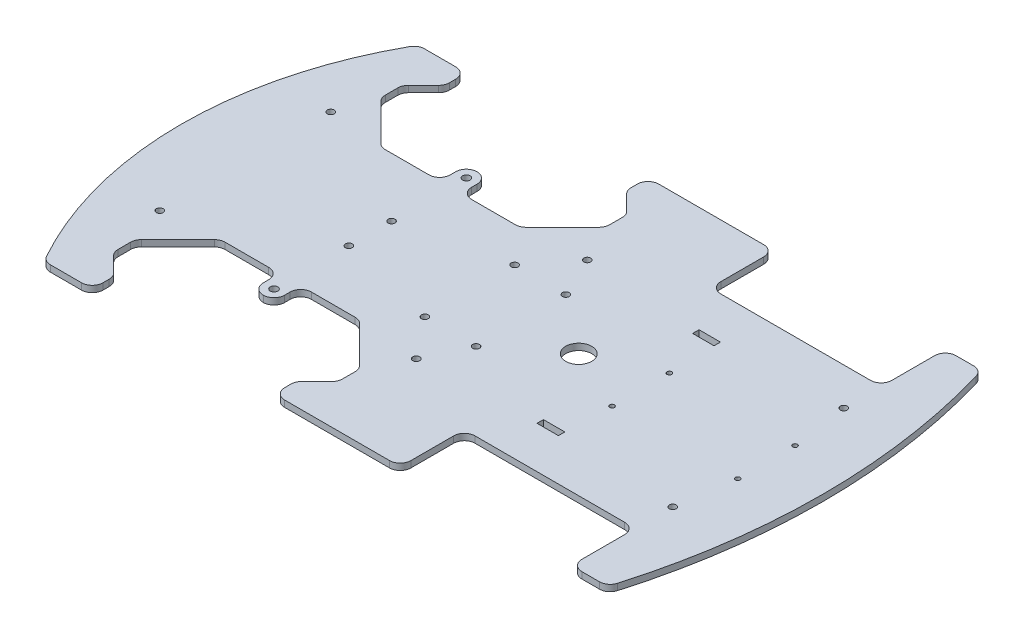
SolidWorks part; units mm, degrees
ref_plane "Front Plane" through (0, 0, 0) normal (0, 0, 1) x (1, 0, 0)
ref_plane "Top Plane" through (0, 0, 0) normal (0, 1, 0) x (1, 0, 0)
ref_plane "Right Plane" through (0, 0, 0) normal (1, 0, 0) x (0, 0, -1)
sketch "Sketch1" plane through (0, 0, 0) normal (0, 1, 0) x (1, 0, 0)
  line L1 (-150, -87.5) -> (150, -87.5) construction
  line L2 (-150, -87.5) -> (-150, 87.5) construction
  line L3 (-150, 87.5) -> (150, 87.5) construction
  line L4 (150, -87.5) -> (150, 87.5) construction
  line L5 (-150, -87.5) -> (150, 87.5) construction
  line L6 (-150, 87.5) -> (150, -87.5) construction
  line L7 (-94.037, 37.4826) -> (-29.037, 37.4826) construction
  line L9 (40, 87.5) -> (40, 57.5)
  line L10 (40, 57.5) -> (120, 57.5)
  line L11 (120, 57.5) -> (120, 87.5)
  line L12 (-150, 0) -> (150, 0) construction
  line L13 (-126.5544, 87.5) -> (-104.0544, 87.5)
  line L14 (120, -57.5) -> (120, -87.5)
  line L19 (54.4, -37.9) -> (64.4, -34.9) construction
  line L20 (54.4, 34.9) -> (64.4, 34.9)
  line L21 (40, -57.5) -> (120, -57.5)
  line L22 (40, -87.5) -> (40, -57.5)
  line L24 (-94.037, -37.4826) -> (-29.037, -37.4826) construction
  line L26 (-61.537, 37.4826) -> (-61.537, -37.4826) construction
  line L27 (54.4, 34.9) -> (54.4, 37.9)
  line L45 (80, 57.5) -> (80, -57.5) construction
  line L47 (40, 87.5) -> (-19.0544, 87.5)
  line L57 (-104.0544, 87.5) -> (-104.0544, 77.5)
  line L58 (-104.0544, 77.5) -> (-114.0544, 67.5)
  line L59 (-114.0544, 67.5) -> (-114.0544, 57.5)
  line L62 (-19.0544, 87.5) -> (-19.0544, 77.5)
  line L63 (-19.0544, 77.5) -> (-9.0544, 67.5)
  line L64 (-9.0544, 67.5) -> (-9.0544, 57.4651)
  line L65 (-9.0544, 57.4651) -> (-29.037, 37.4826)
  line L66 (-114.0544, 57.5) -> (-94.037, 37.4826)
  line L67 (-126.5544, -87.5) -> (-104.0544, -87.5)
  line L68 (-104.0544, -87.5) -> (-104.0544, -77.5)
  line L69 (-104.0544, -77.5) -> (-114.0544, -67.5)
  line L70 (-114.0544, -67.5) -> (-114.0544, -57.5)
  line L71 (-114.0544, -57.5) -> (-94.037, -37.4826)
  line L74 (-9.0544, -57.4651) -> (-29.037, -37.4826)
  line L75 (-9.0544, -67.5) -> (-9.0544, -57.4651)
  line L76 (-19.0544, -77.5) -> (-9.0544, -67.5)
  line L77 (-19.0544, -87.5) -> (-19.0544, -77.5)
  line L78 (40, -87.5) -> (-19.0544, -87.5)
  line L79 (120, -87.5) -> (136.956, -87.5)
  line L80 (120, 87.5) -> (136.956, 87.5)
  line L81 (54.4, 37.9) -> (64.4, 37.9)
  line L82 (64.4, 34.9) -> (64.4, 37.9)
  line L83 (54.4, 34.9) -> (64.4, 37.9) construction
  line L84 (54.4, 37.9) -> (64.4, 34.9) construction
  line L85 (54.4, -34.9) -> (64.4, -37.9) construction
  line L86 (64.4, -34.9) -> (64.4, -37.9)
  line L87 (54.4, -37.9) -> (64.4, -37.9)
  line L88 (54.4, -34.9) -> (54.4, -37.9)
  line L89 (54.4, -34.9) -> (64.4, -34.9)
  line L90 (-29.037, -37.4826) -> (-56.537, -37.4826)
  line L97 (-94.037, -37.4826) -> (-66.537, -37.4826)
  line L98 (-66.537, -37.4826) -> (-66.537, -50)
  line L99 (-66.537, -50) -> (-56.537, -50)
  line L100 (-56.537, -50) -> (-56.537, -37.4826)
  line L101 (-29.037, 37.4826) -> (-56.537, 37.4826)
  line L102 (-56.537, 50) -> (-56.537, 37.4826)
  line L103 (-66.537, 50) -> (-56.537, 50)
  line L104 (-66.537, 37.4826) -> (-66.537, 50)
  line L105 (-94.037, 37.4826) -> (-66.537, 37.4826)
  arc A7 (-126.5544, 87.5) -> (-126.5544, -87.5) centre (25, 0) ccw
  arc A10 (136.956, 87.5) -> (136.956, -87.5) centre (-150, 0) cw
  circle A11 centre (-120, -40) radius 1.6
  circle A12 centre (0, -40) radius 1.6
  circle A13 centre (120, -40) radius 1.6
  circle A14 centre (120, 40) radius 1.6
  circle A15 centre (0, 40) radius 1.6
  circle A16 centre (-120, 40) radius 1.6
  circle A17 centre (-15, 21) radius 1.6
  circle A18 centre (9, 21) radius 1.6
  circle A19 centre (9, -21) radius 1.6
  circle A20 centre (-15, -21) radius 1.6
  circle A21 centre (123.8, 13.4) radius 1.1
  circle A22 centre (65, 13.4) radius 1.1
  circle A23 centre (65, -13.4) radius 1.1
  circle A24 centre (123.8, -13.4) radius 1.1
  circle A25 centre (-61.537, -45) radius 1.75
  circle A26 centre (-61.537, 45) radius 1.75
  circle A27 centre (-61.537, -10) radius 1.6
  circle A28 centre (-61.537, 10) radius 1.6
  circle A29 centre (36, 0) radius 6.1
  point P0 (0, 0)
  point P18 (59.4, 36.4)
  point P37 (59.4, -36.4)
  point P38 (0, 0)
  dimension "D15" = 21.1
  dimension "D19" = 3.2
  dimension "D21" = 3.2
  dimension "D23" = 120
  dimension "D24" = 175
  dimension "D26" = 3.2
  dimension "D28" = 85
  dimension "D34" = 300
  dimension "D22" = 3.2
  dimension "D16" = 3.2
  dimension "D38" = 3.2
  dimension "D40" = 2.2
  dimension "D47" = 3.5
  dimension "D44" = 36
  dimension "D45" = 12.2
  dimension "D1" = 175
  dimension "D2" = 300
  dimension "D4" = 10
  dimension "D5" = 135
  dimension "D6" = 135
  dimension "D7" = 80
  dimension "D8" = 30
  dimension "D9" = 22.5
  dimension "D10" = 30
  dimension "D11" = 10
  dimension "D12" = 10
  dimension "D13" = 3
  dimension "D14" = 20.6
  dimension "D17" = 135
  dimension "D18" = 65
  dimension "D20" = 10
  dimension "D25" = 10
  dimension "D27" = 120
  dimension "D29" = 10
  dimension "D30" = 135
  dimension "D31" = 10.0349
  dimension "D32" = 27.5
  dimension "D33" = 10
  dimension "D35" = 40
  dimension "D36" = 21
  dimension "D37" = 15
  dimension "D39" = 24
  dimension "D41" = 13.4
  dimension "D42" = 58.8
  dimension "D43" = 65
  dimension "D48" = 45
  dimension "D49" = 27.5
  dimension "D50" = 50
extrude "Boss-Extrude1" add sketch "Sketch1" along normal blind 3
fillet "Fillet1" radius 5 40 edges at (-104.0544, 1.5, -87.5) (-104.0544, 1.5, -77.5) (-114.0544, 1.5, -67.5) (-114.0544, 1.5, -57.5) (-9.0544, 1.5, -57.4651) (-9.0544, 1.5, -67.5) (-19.0544, 1.5, -77.5) (-19.0544, 1.5, -87.5) (40, 1.5, -87.5) (40, 1.5, -57.5) (120, 1.5, -57.5) (120, 1.5, -87.5) (136.956, 1.5, -87.5) (136.956, 1.5, 87.5) (120, 1.5, 87.5) (120, 1.5, 57.5) (40, 1.5, 57.5) (40, 1.5, 87.5) (-19.0544, 1.5, 87.5) (-19.0544, 1.5, 77.5) (-9.0544, 1.5, 67.5) (-9.0544, 1.5, 57.4651) (-114.0544, 1.5, 57.5) (-114.0544, 1.5, 67.5) (-104.0544, 1.5, 77.5) (-104.0544, 1.5, 87.5) (-126.5544, 1.5, 87.5) (-126.5544, 1.5, -87.5) (-56.537, 1.5, -50) (-94.037, 1.5, -37.4826) (-29.037, 1.5, -37.4826) (-66.537, 1.5, -50) (-29.037, 1.5, 37.4826) (-94.037, 1.5, 37.4826) (-56.537, 1.5, 50) (-66.537, 1.5, 50) (-66.537, 1.5, -37.4826) (-56.537, 1.5, -37.4826) (-66.537, 1.5, 37.4826) (-56.537, 1.5, 37.4826)
